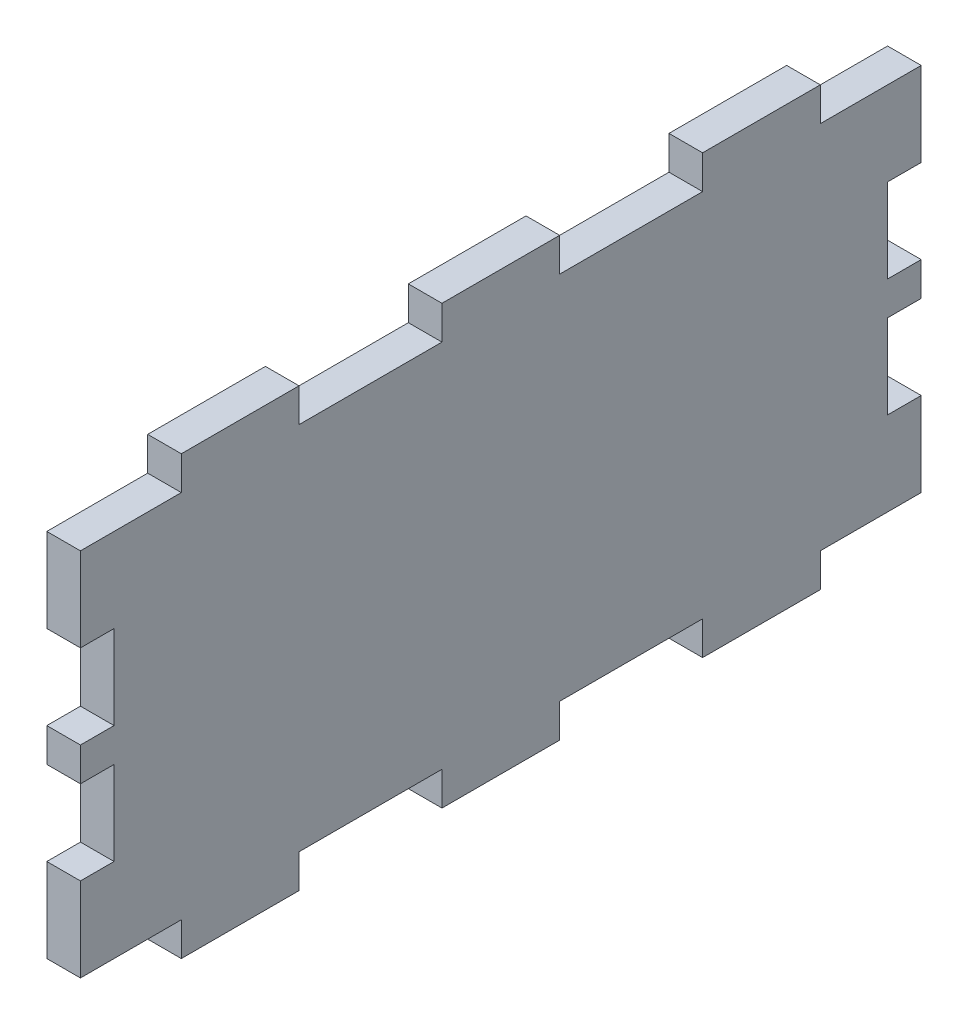
SolidWorks part; units mm, degrees
ref_plane "Front Plane" through (0, 0, 0) normal (0, 0, 1) x (1, 0, 0)
ref_plane "Top Plane" through (0, 0, 0) normal (0, 1, 0) x (1, 0, 0)
ref_plane "Right Plane" through (0, 0, 0) normal (1, 0, 0) x (0, 0, -1)
sketch "Sketch1" plane through (0, 0, 0) normal (1, 0, 0) x (0, 0, -1)
  line L1 (-25, 11) -> (25, 11)
  line L2 (-25, 11) -> (-25, -11)
  line L3 (-25, -11) -> (25, -11)
  line L4 (25, 11) -> (25, -11)
  line L5 (-25, 11) -> (25, -11) construction
  line L6 (-25, -11) -> (25, 11) construction
  line L7 (-19, -11) -> (-12, -11)
  line L8 (-19, -11) -> (-19, -13)
  line L9 (-19, -13) -> (-12, -13)
  line L10 (-12, -11) -> (-12, -13)
  line L11 (-3.5, -11) -> (3.5, -11)
  line L12 (-3.5, -11) -> (-3.5, -13)
  line L13 (-3.5, -13) -> (3.5, -13)
  line L14 (3.5, -11) -> (3.5, -13)
  line L15 (12, -11) -> (19, -11)
  line L16 (12, -11) -> (12, -13)
  line L17 (12, -13) -> (19, -13)
  line L18 (19, -11) -> (19, -13)
  line L19 (-19, 11) -> (-12, 11)
  line L20 (-19, 11) -> (-19, 13)
  line L21 (-19, 13) -> (-12, 13)
  line L22 (-12, 11) -> (-12, 13)
  line L23 (-3.5, 11) -> (3.5, 11)
  line L24 (-3.5, 11) -> (-3.5, 13)
  line L25 (-3.5, 13) -> (3.5, 13)
  line L26 (3.5, 11) -> (3.5, 13)
  line L27 (12, 11) -> (19, 11)
  line L28 (12, 11) -> (12, 13)
  line L29 (12, 13) -> (19, 13)
  line L30 (19, 11) -> (19, 13)
  line L31 (-25, -1) -> (-23, -1)
  line L32 (-25, -1) -> (-25, -6)
  line L33 (-25, -6) -> (-23, -6)
  line L34 (-23, -1) -> (-23, -6)
  line L35 (23, -1) -> (25, -1)
  line L36 (23, -1) -> (23, -6)
  line L37 (23, -6) -> (25, -6)
  line L38 (25, -1) -> (25, -6)
  line L39 (-25, 6) -> (-23, 6)
  line L40 (-25, 6) -> (-25, 1)
  line L41 (-25, 1) -> (-23, 1)
  line L42 (-23, 6) -> (-23, 1)
  line L43 (23, 6) -> (25, 6)
  line L44 (23, 6) -> (23, 1)
  line L45 (23, 1) -> (25, 1)
  line L46 (25, 6) -> (25, 1)
  point P0 (0, 0)
  dimension "D1" = 50
  dimension "D2" = 7
  dimension "D3" = 7
  dimension "D4" = 7
  dimension "D5" = 7
  dimension "D6" = 7
  dimension "D7" = 7
  dimension "D8" = 6
  dimension "D9" = 8.5
  dimension "D10" = 8.5
  dimension "D11" = 6
  dimension "D12" = 6
  dimension "D13" = 8.5
  dimension "D14" = 8.5
  dimension "D15" = 6
  dimension "D16" = 22
  dimension "D17" = 2
  dimension "D18" = 2
  dimension "D19" = 2
  dimension "D20" = 2
  dimension "D21" = 2
  dimension "D22" = 2
  dimension "D23" = 5
  dimension "D24" = 5
  dimension "D25" = 5
  dimension "D26" = 5
  dimension "D27" = 5
  dimension "D28" = 5
  dimension "D29" = 5
  dimension "D30" = 5
  dimension "D31" = 0
  dimension "D32" = 0
  dimension "D33" = 46
  dimension "D34" = 0
  dimension "D35" = 0
  dimension "D37" = 0
  dimension "D38" = 0
extrude "Boss-Extrude1" add sketch "Sketch1" along normal blind 2 contours L4 L1 L2 L3 | L1 L26 L25 L24 | L1 L30 L29 L28 | L18 L3 L16 L17 | L14 L3 L12 L13 | L10 L3 L8 L9 | L22 L21 L20 L19 region at (0, 0, 0) region at (0, 12, 0) region at (0, 12, -15.5) region at (0, -12, 15.5) region at (0, -12, 0) region at (0, -12, -15.5)
